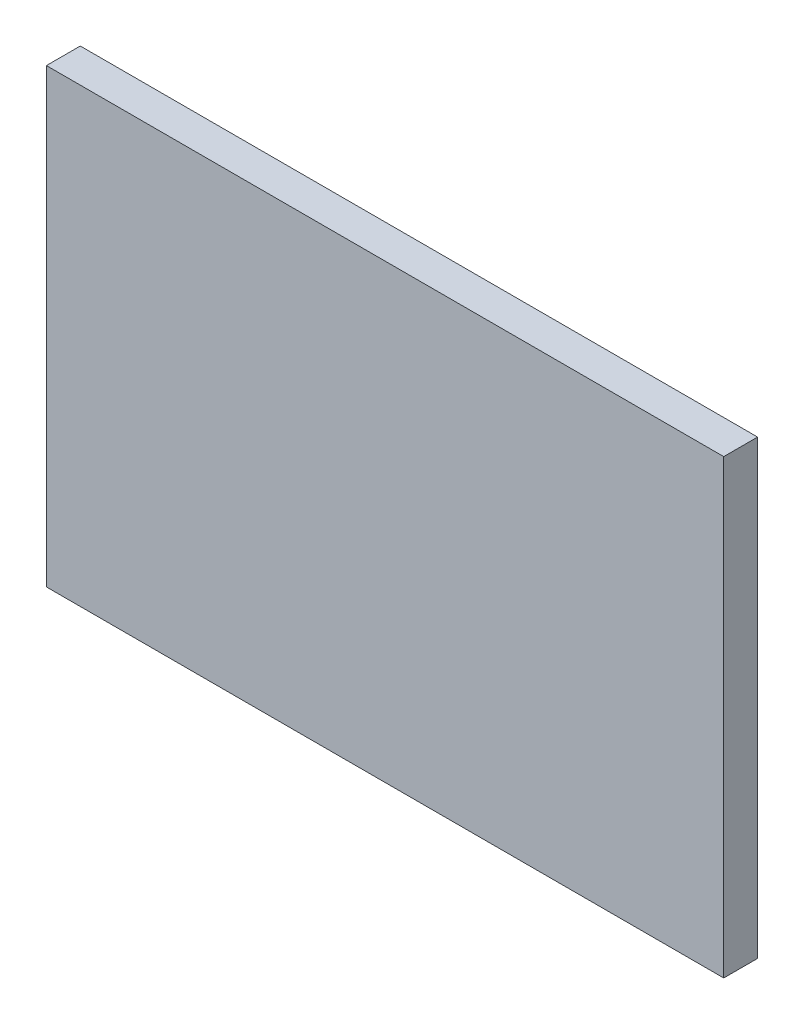
SolidWorks part; units mm, degrees
ref_plane "Plano frontal" through (0, 0, 0) normal (0, 0, 1) x (1, 0, 0)
ref_plane "Plano superior" through (0, 0, 0) normal (0, 1, 0) x (1, 0, 0)
ref_plane "Plano direito" through (0, 0, 0) normal (1, 0, 0) x (0, 0, -1)
sketch "Esboço1" plane through (0, 0, 0) normal (0, 0, 1) x (1, 0, 0)
  line L1 (0, 0) -> (60, 0)
  line L2 (0, 0) -> (0, 40)
  line L3 (0, 40) -> (60, 40)
  line L4 (60, 0) -> (60, 40)
  dimension "D1" = 40
  dimension "D2" = 60
extrude "Ressalto-extrusão1" add sketch "Esboço1" along normal blind 3
